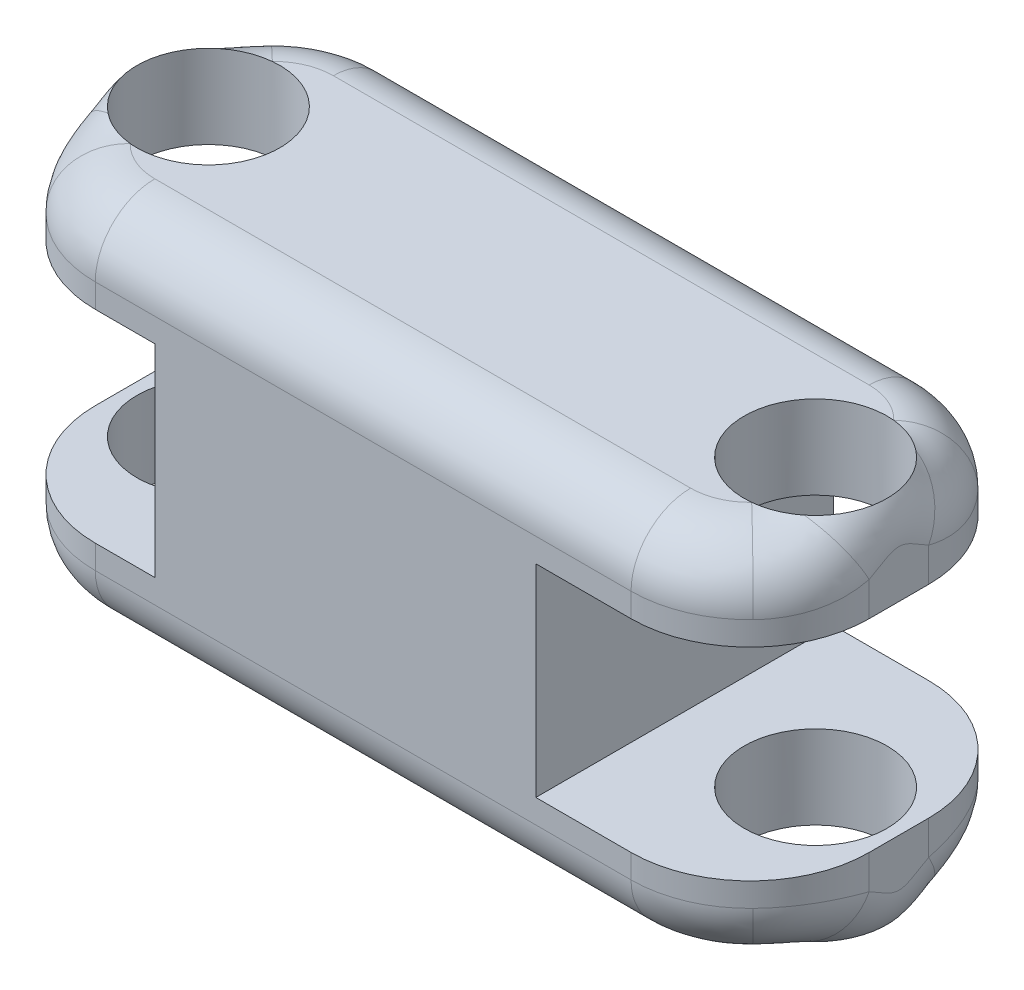
SolidWorks part; units mm, degrees
ref_plane "Alzado" through (0, 0, 0) normal (0, 0, 1) x (1, 0, 0)
ref_plane "Planta" through (0, 0, 0) normal (0, 1, 0) x (1, 0, 0)
ref_plane "Vista lateral" through (0, 0, 0) normal (1, 0, 0) x (0, 0, -1)
sketch "Croquis1" plane through (0, 0, 0) normal (0, 0, 1) x (1, 0, 0)
  line L0 (-44.878, 8.5677) -> (-29.878, 8.5677)
  line L1 (-44.878, 15.5677) -> (20.122, 15.5677)
  line L2 (-44.878, 15.5677) -> (-44.878, 8.5677)
  line L3 (-44.878, -15.4323) -> (20.122, -15.4323)
  line L4 (20.122, 15.5677) -> (20.122, 8.5677)
  line L5 (-29.878, 8.5677) -> (-29.878, -8.4323)
  line L6 (-29.878, -8.4323) -> (-44.878, -8.4323)
  line L7 (-44.878, -8.4323) -> (-44.878, -15.4323)
  line L8 (20.122, -8.4323) -> (20.122, -15.4323)
  line L9 (20.122, 8.5677) -> (2.122, 8.5677)
  line L11 (20.122, -8.4323) -> (2.122, -8.4323)
  line L12 (2.122, 8.5677) -> (2.122, -8.4323)
  dimension "D1" = 65
  dimension "D2" = 31
  dimension "D3" = 15
  dimension "D4" = 7
  dimension "D5" = 7
  dimension "D6" = 18
extrude "Saliente-Extruir1" add sketch "Croquis1" along normal blind 25
sketch "Croquis2" plane through (0, 15.5677, 0) normal (0, 1, 0) x (1, 0, 0)
  line L0 (-44.878, -25) -> (-44.878, 0) construction
  line L1 (20.122, 0) -> (-44.878, 0) construction
  line L2 (20.122, -25) -> (20.122, 0) construction
  circle A0 centre (-37.878, -12.5) radius 6
  circle A1 centre (13.122, -12.5) radius 6
  dimension "D1" = 12
  dimension "D2" = 7
  dimension "D3" = 12.5
  dimension "D4" = 12
  dimension "D5" = 12.5
  dimension "D6" = 7
extrude "Cortar-Extruir1" cut sketch "Croquis2" against normal through all
fillet "Redondeo1" radius 10 8 edges at (-44.878, 12.0677, 0) (-44.878, -11.9323, 0) (-44.878, -11.9323, 25) (-44.878, 12.0677, 25) (20.122, 12.0677, 0) (20.122, -11.9323, 0) (20.122, -11.9323, 25) (20.122, 12.0677, 25)
fillet "Redondeo3" radius 5 12 edges at (-41.9491, -15.4323, 22.0711) (-41.9491, -15.4323, 2.9289) (-41.9491, 15.5677, 2.9289) (-41.9491, 15.5677, 22.0711) (-12.378, -15.4323, 25) (-12.378, -15.4323, 0) (-12.378, 15.5677, 0) (-12.378, 15.5677, 25) (17.193, -15.4323, 22.0711) (17.193, -15.4323, 2.9289) (17.193, 15.5677, 22.0711) (17.193, 15.5677, 2.9289)
